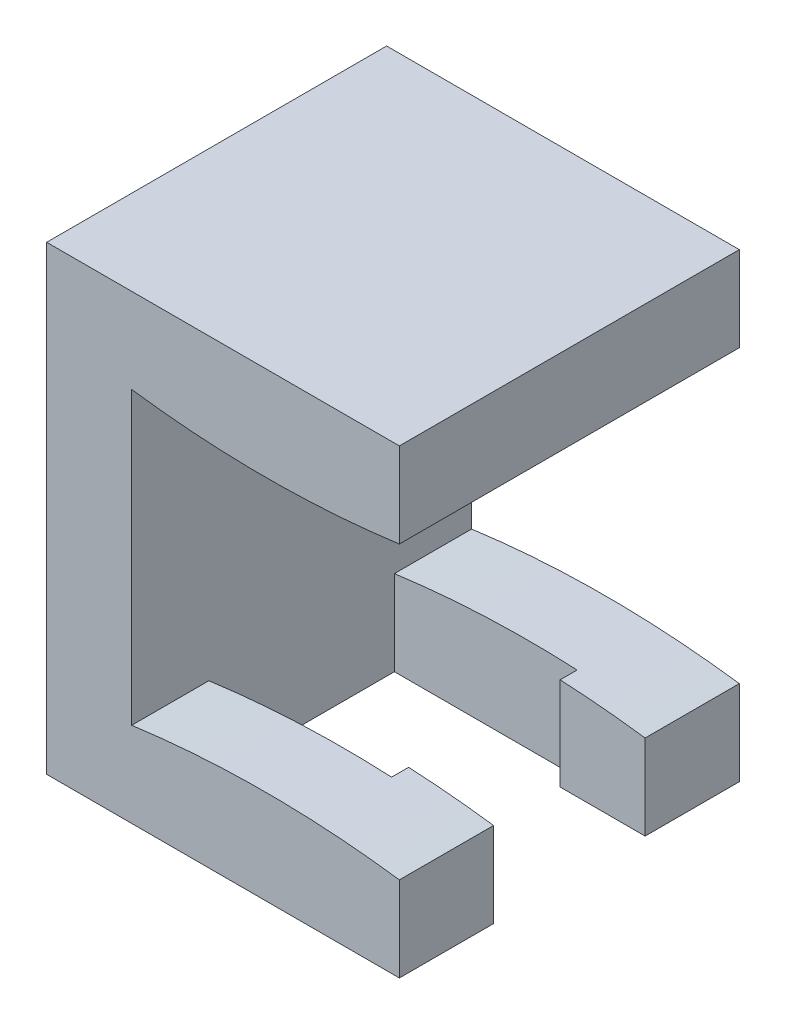
SolidWorks part; units mm, degrees
ref_plane "Front Plane" through (0, 0, 0) normal (0, 0, 1) x (1, 0, 0)
ref_plane "Top Plane" through (0, 0, 0) normal (0, 1, 0) x (1, 0, 0)
ref_plane "Right Plane" through (0, 0, 0) normal (1, 0, 0) x (0, 0, -1)
sketch "Sketch1" plane through (0, 0, 0) normal (0, 0, 1) x (1, 0, 0)
  line L2 (-159.7982, 8.1335) -> (-172.2482, 8.1335)
  line L3 (-172.2482, 8.1335) -> (-172.2482, -8.1335)
  line L7 (-169.2482, -22.8519) -> (-169.2482, 5.1335) construction
  line L12 (-169.2482, 4.7625) -> (-169.2482, 1.5875) construction
  line L23 (-159.7982, 5.1335) -> (-159.7982, 8.1335)
  line L28 (-164.5232, 4.8125) -> (-144.5007, 4.8125) construction
  line L29 (-156.5482, 4.7625) -> (-169.2482, 4.7625) construction
  line L30 (-169.2482, 5.1335) -> (-169.2482, 4.7625)
  line L32 (-158.1026, 4.7625) -> (-158.1026, -4.7625) construction
  line L33 (-169.2482, -4.7625) -> (-156.5482, -4.7625) construction
  line L34 (-169.2482, 4.7625) -> (-169.2482, -4.7625)
  line L35 (-172.2482, 0) -> (-169.2482, 0) construction
  line L36 (-169.2482, -5.1335) -> (-169.2482, -4.7625)
  line L37 (-159.7982, -5.1335) -> (-159.7982, -8.1335)
  line L38 (-159.7982, -8.1335) -> (-172.2482, -8.1335)
  line L39 (-159.7982, 4.7625) -> (-159.7982, 1.5875) construction
  arc A5 (-169.2482, 5.1335) -> (-159.7982, 5.1335) centre (-164.5232, 39.752) ccw
  arc A6 (-169.2482, -5.1335) -> (-159.7982, -5.1335) centre (-164.5232, -39.752) cw
  point P18 (-158.1026, 0)
  dimension "D4" = 3
  dimension "D3" = 3
  dimension "D1" = 0.05
extrude "MainBody" add sketch "Sketch1" along normal mid plane 12
sketch "Sketch2" plane through (0, -8.1335, 0) normal (0, -1, 0) x (1, 0, 0)
  line L11 (-162.7982, -2.675) -> (-159.7982, -2.675)
  line L12 (-162.7982, -3.275) -> (-162.7982, -2.675)
  line L13 (-169.2482, -3.275) -> (-162.7982, -3.275)
  line L14 (-162.8982, 3.175) -> (-169.2482, 3.175) construction
  line L19 (-169.2482, 3.275) -> (-162.7982, 3.275)
  line L20 (-169.2482, 6) -> (-169.2482, -6) construction
  line L21 (-162.7982, 3.275) -> (-162.7982, 2.675)
  line L22 (-162.7982, 2.675) -> (-159.7982, 2.675)
  line L23 (-159.7982, 2.675) -> (-159.7982, -2.675)
  line L24 (-169.2482, 3.275) -> (-169.2482, -3.275)
  line L25 (-169.2482, -63.5) -> (-169.2482, 63.5) construction
  line L26 (-169.2482, 0) -> (-159.7982, 0) construction
  line L27 (-162.8982, -3.175) -> (-162.8982, 3.175) construction
  line L28 (-159.7982, 6) -> (-159.7982, -6) construction
  dimension "D1" = 0.1
  dimension "D2" = 0.1
  dimension "D3" = 0.5
extrude "Grip" cut sketch "Sketch2" against normal up to next
equation "\"HookThickness\"=3"
equation "\"HookOverhang\"=3"
equation "\"HookHeight\"=5"
equation "\"D3@Sketch1\"=\"HookThickness\""
equation "\"D4@Sketch1\"=\"HookThickness\""
equation "\"D1@Sketch2\"=0.1mm"
equation "\"D2@Sketch2\"=0.1mm"
equation "\"D3@Sketch2\"=0.5mm"
